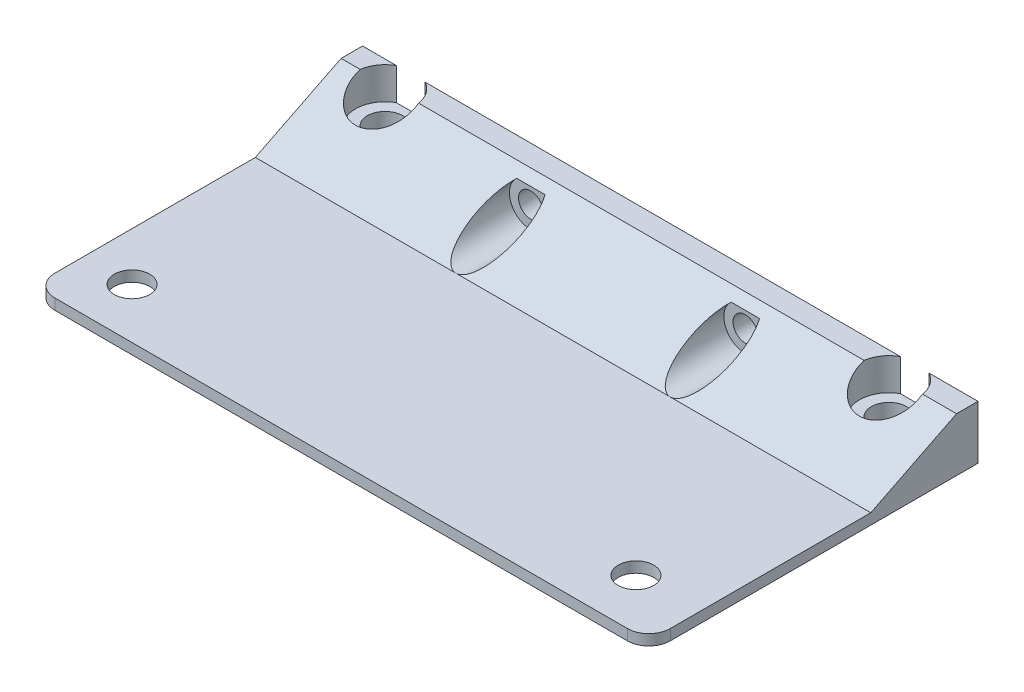
SolidWorks part; units mm, degrees
ref_plane "Front Plane" through (0, 0, 0) normal (0, 0, 1) x (1, 0, 0)
ref_plane "Top Plane" through (0, 0, 0) normal (0, 1, 0) x (1, 0, 0)
ref_plane "Right Plane" through (0, 0, 0) normal (1, 0, 0) x (0, 0, -1)
sketch "Sketch1" plane through (0, 0, 0) normal (0, 1, 0) x (1, 0, 0)
  line L0 (4.5, 28.3) -> (4.5, 4.7) construction
  line L1 (0, 0) -> (57.4, 0)
  line L2 (0, 0) -> (0, 33)
  line L3 (0, 33) -> (57.4, 33)
  line L4 (57.4, 0) -> (57.4, 33)
  circle A0 centre (4.5, 28.3) radius 1.65
  circle A1 centre (51.5, 28.3) radius 1.65
  circle A2 centre (4.5, 4.7) radius 1.65
  circle A3 centre (51.5, 4.7) radius 1.65
  point P13 (0, 16.5)
  point P14 (4.5, 16.5)
  dimension "D3" = 3.3
  dimension "D4" = 47
  dimension "D5" = 23.6
  dimension "D6" = 4.5
  dimension "D1" = 57.4
  dimension "D2" = 33
extrude "Boss-Extrude1" add sketch "Sketch1" along normal blind 1
sketch "Sketch2" plane through (0, 1, 0) normal (0, 1, 0) x (1, 0, 0)
  line L0 (57.4, 0) -> (57.4, 33) construction
  line L1 (0, 33) -> (57.4, 33)
  line L2 (0, 33) -> (0, 30.7)
  line L3 (0, 30.7) -> (57.4, 30.7)
  line L4 (57.4, 33) -> (57.4, 30.7)
  dimension "D1" = 2.3
extrude "Cut-Extrude1" cut sketch "Sketch2" against normal up to next
sketch "Sketch3" plane through (57.4, 0, 0) normal (1, 0, 0) x (0, 0, -1)
  line L0 (30.7, 1) -> (30.7, 5)
  line L1 (30.7, 5) -> (28.7, 5)
  line L2 (28.7, 5) -> (20.7, 1)
  line L3 (0, 1) -> (30.7, 1) construction
  line L4 (20.7, 1) -> (30.7, 1)
  dimension "D1" = 4
  dimension "D2" = 10
  dimension "D3" = 2
extrude "Boss-Extrude2" add sketch "Sketch3" against normal up to surface (57.4 mm away) up to face at (0, 0.5, -15.35)
fillet "Fillet1" radius 2 2 edges at (0, 0.5, 0) (57.4, 0.5, 0)
sketch "Sketch4" plane through (0, 0, 0) normal (0, -1, 0) x (-1, 0, 0)
  circle A0 centre (-4.5, 28.3) radius 1.65
  circle A1 centre (-51.5, 28.3) radius 1.65
  dimension "D1" = 3.3
extrude "Cut-Extrude2" cut sketch "Sketch4" against normal blind 2
sketch "Sketch5" plane through (0, 2, 0) normal (0, -1, 0) x (-1, 0, 0)
  circle A0 centre (-4.5, 28.3) radius 2.75
  circle A1 centre (-51.5, 28.3) radius 2.75
  dimension "D1" = 5.5
extrude "Cut-Extrude3" cut sketch "Sketch5" against normal up to next
sketch "Sketch6" plane through (0, 0, -30.7) normal (0, 0, -1) x (-1, 0, 0)
  circle A0 centre (-38.7, 3) radius 1.15
  circle A1 centre (-18.7, 3) radius 1.15
  dimension "D1" = 2.3
extrude "Cut-Extrude4" cut sketch "Sketch6" against normal blind 3
sketch "Sketch9" plane through (0, 0, -27.7) normal (0, 0, -1) x (-1, 0, 0)
  circle A0 centre (-38.7, 3) radius 2
  circle A1 centre (-18.7, 3) radius 2
  dimension "D1" = 4
extrude "Cut-Extrude5" cut sketch "Sketch9" against normal through all
